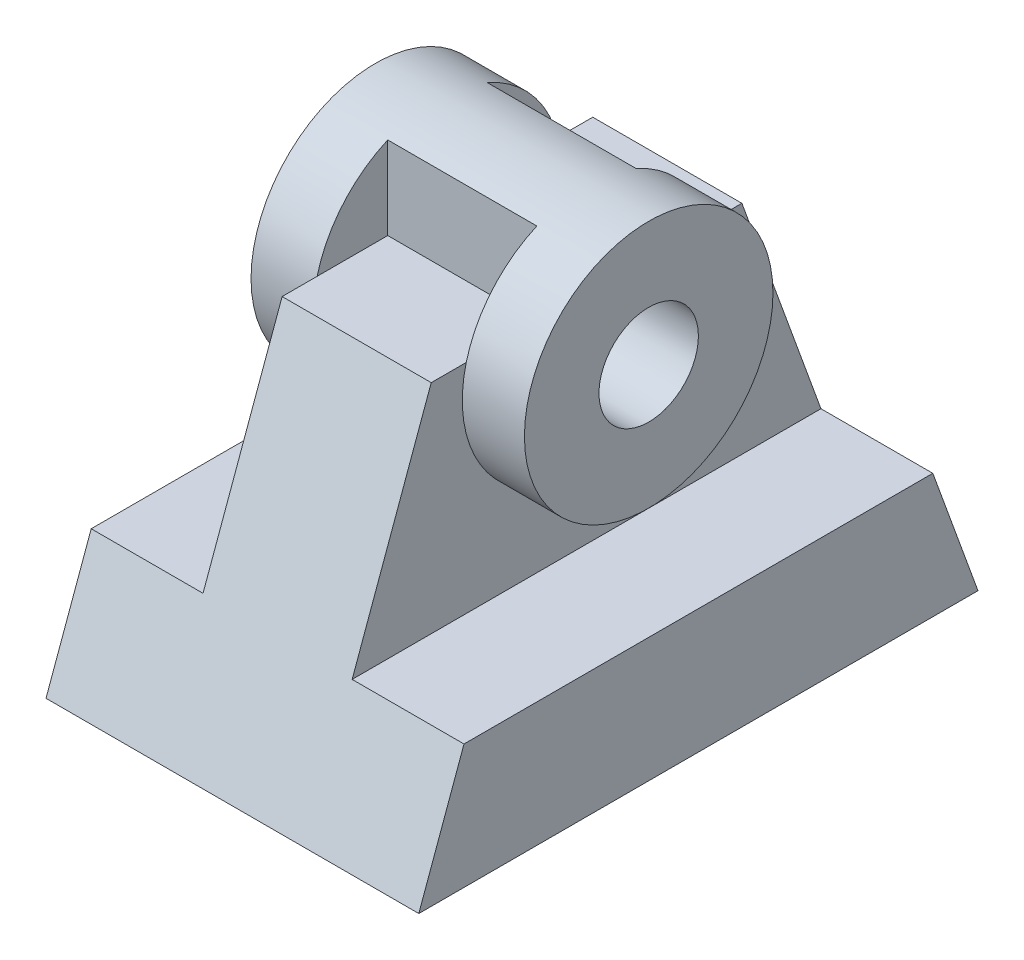
SolidWorks part; units mm, degrees
ref_plane "Alzado" through (0, 0, 0) normal (0, 0, 1) x (1, 0, 0)
ref_plane "Planta" through (0, 0, 0) normal (0, 1, 0) x (1, 0, 0)
ref_plane "Vista lateral" through (0, 0, 0) normal (1, 0, 0) x (0, 0, -1)
sketch "Croquis1" plane through (0, 0, 0) normal (1, 0, 0) x (0, 0, -1)
  line L0 (0, 0) -> (0, 55) construction
  line L1 (45, 0) -> (-45, 0)
  line L2 (-45, 0) -> (-25, 55)
  line L3 (-25, 55) -> (25, 55)
  line L4 (45, 0) -> (25, 55)
  dimension "D1" = 90
  dimension "D2" = 55
  dimension "D3" = 50
extrude "Saliente-Extruir1" add sketch "Croquis1" along normal mid plane 60
ref_plane "Plano1" through (0, 0, 45) normal (0, 0, 1) x (1, 0, 0)
sketch "Croquis2" plane through (0, 0, 45) normal (0, 0, 1) x (1, 0, 0)
  line L0 (30, 0) -> (-30, 0) construction
  line L1 (-30, 55) -> (-12, 55)
  line L2 (-30, 55) -> (-30, 20)
  line L3 (-30, 20) -> (-12, 20)
  line L4 (-12, 55) -> (-12, 20)
  line L5 (12, 20) -> (30, 20)
  line L6 (12, 20) -> (12, 55)
  line L7 (12, 55) -> (30, 55)
  line L8 (30, 20) -> (30, 55)
  point P13 (21, 20)
  point P14 (-21, 20)
  dimension "D1" = 24
  dimension "D2" = 18
  dimension "D3" = 20
extrude "Cortar-Extruir1" cut sketch "Croquis2" against normal through all
sketch "Croquis3" plane through (0, 0, 0) normal (1, 0, 0) x (0, 0, -1)
  line L0 (-45, 0) -> (45, 0) construction
  circle A0 centre (0, 50) radius 20
  circle A1 centre (0, 50) radius 8
  dimension "D2" = 16
  dimension "D3" = 40
  dimension "D1" = 50
extrude "Saliente-Extruir2" add sketch "Croquis3" along normal mid plane 44 contours A0
extrude "Cortar-Extruir2" cut sketch "Croquis3<3>" against normal through all and the other way through all contours A1
sketch "Croquis3<3>" plane through (0, 0, 0) normal (1, 0, 0) x (0, 0, -1) same geometry as "Croquis3"
ref_plane "Plano2" through (0, 70, 0) normal (0, 1, 0) x (1, 0, 0)
sketch "Croquis4" plane through (0, 70, 0) normal (0, 1, 0) x (1, 0, 0)
  line L0 (12, 25) -> (-12, 25) construction
  line L1 (-12, 25) -> (12, 25)
  line L2 (-12, 25) -> (-12, -25)
  line L3 (-12, -25) -> (12, -25)
  line L4 (12, 25) -> (12, -25)
  line L5 (-12, 37.7273) -> (-12, -37.7273) construction
  line L6 (12, 37.7273) -> (12, -37.7273) construction
  line L8 (-12, 8) -> (12, 8)
  line L9 (-12, 8) -> (-12, -8)
  line L10 (-12, -8) -> (12, -8)
  line L11 (12, 8) -> (12, -8)
  dimension "D1" = 16
  dimension "D2" = 17
extrude "Cortar-Extruir4" cut sketch "Croquis4" against normal up to surface (15 mm away) contours L10 L2 L3 L4 | L2 L8 L4 L1 region at (0, 70, -16.5) region at (0, 70, 16.5) up to face at (0, 55, 22.1825)
